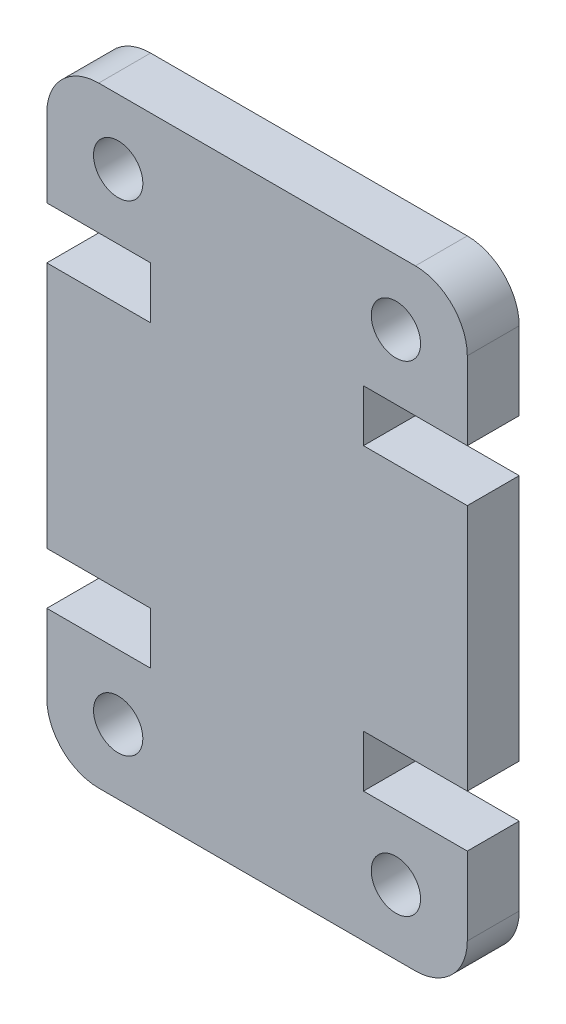
SolidWorks part; units mm, degrees
ref_plane "Front Plane" through (0, 0, 0) normal (0, 0, 1) x (1, 0, 0)
ref_plane "Top Plane" through (0, 0, 0) normal (0, 1, 0) x (1, 0, 0)
ref_plane "Right Plane" through (0, 0, 0) normal (1, 0, 0) x (0, 0, -1)
sketch "Sketch1" plane through (0, 0, 0) normal (0, 0, 1) x (1, 0, 0)
  line L0 (8.1, 23.525) -> (8.1, 0) construction
  line L1 (0, 11.7625) -> (16.2, 11.7625) construction
  line L2 (16.2, 5) -> (16.2, 2)
  line L3 (12.2, 5) -> (16.2, 5)
  line L4 (16.2, 7) -> (12.2, 7)
  line L5 (12.2, 7) -> (12.2, 5)
  line L6 (16.2, 7) -> (16.2, 16.525)
  line L7 (0, 18.525) -> (0, 21.525)
  line L8 (4, 18.525) -> (0, 18.525)
  line L9 (0, 16.525) -> (4, 16.525)
  line L10 (4, 16.525) -> (4, 18.525)
  line L11 (2, 23.525) -> (14.2, 23.525)
  line L12 (12.2, 16.525) -> (12.2, 18.525)
  line L13 (16.2, 16.525) -> (12.2, 16.525)
  line L14 (12.2, 18.525) -> (16.2, 18.525)
  line L15 (16.2, 18.525) -> (16.2, 21.525)
  line L20 (0, 7) -> (0, 16.525)
  line L23 (2, 0) -> (14.2, 0)
  line L30 (4, 7) -> (4, 5)
  line L32 (0, 7) -> (4, 7)
  line L33 (4, 5) -> (0, 5)
  line L39 (0, 5) -> (0, 2)
  circle A0 centre (13.45, 2.5) radius 0.95
  arc A2 (16.2, 2) -> (14.2, 0) centre (14.2, 2) cw
  circle A4 centre (2.75, 21.025) radius 0.95
  arc A5 (0, 21.525) -> (2, 23.525) centre (2, 21.525) cw
  arc A7 (16.2, 21.525) -> (14.2, 23.525) centre (14.2, 21.525) ccw
  circle A9 centre (13.45, 21.025) radius 0.95
  arc A11 (0, 2) -> (2, 0) centre (2, 2) ccw
  circle A13 centre (2.75, 2.5) radius 0.95
  point P18 (8.1, 11.7625)
  dimension "D2" = 2
  dimension "D4" = 1.9
  dimension "D3" = 2.75
  dimension "D5" = 8.1
  dimension "D6" = 2.5
  dimension "D10" = 11.7625
  dimension "D7" = 5
extrude "Boss-Extrude1" add sketch "Sketch1" along normal blind 2
equation "\"D10@Sketch1\"= ( \"HL@parametersSketch@prostheticParameters.SLDPRT\" * 0.165 - 3 - 4 ) / 2 'MIP length - Sil. Sht MIP - Sil. Sht DIP"
equation "\"D5@Sketch1\"= \"fingerWidth@parametersSketch@prostheticParameters.SLDPRT\" / 2'MIP width"
equation "\"D4@Sketch1\"= 1.5 + \"tol1@parametersSketch@prostheticParameters.SLDPRT\""
